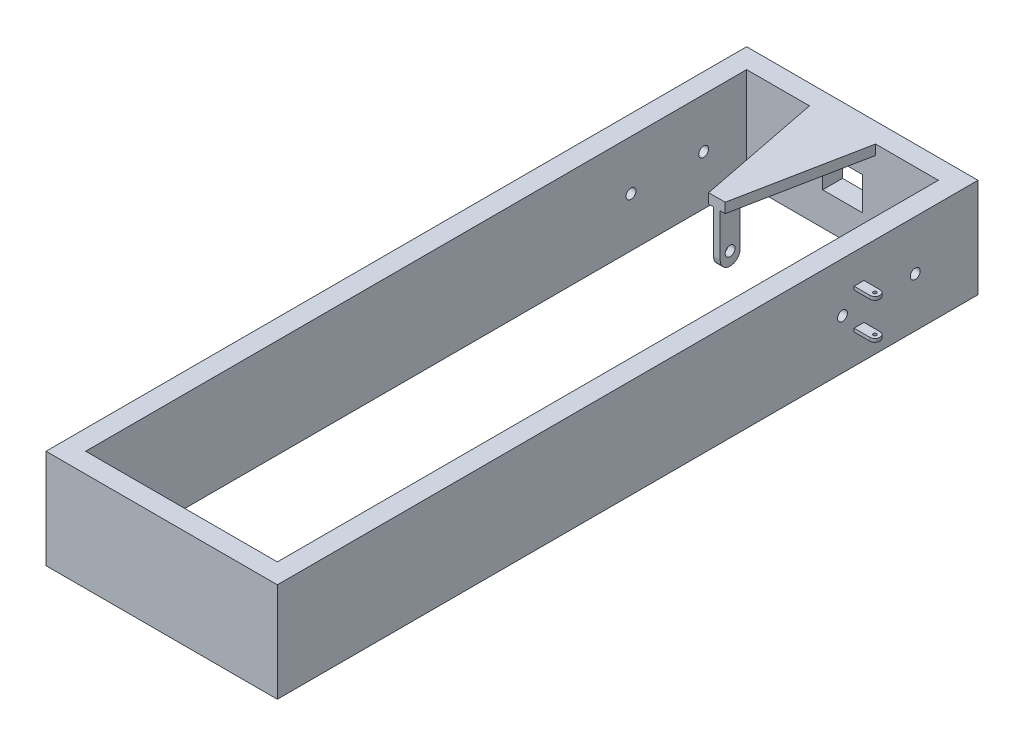
SolidWorks part; units mm, degrees
ref_plane "Front Plane" through (0, 0, 0) normal (0, 0, 1) x (1, 0, 0)
ref_plane "Top Plane" through (0, 0, 0) normal (0, 1, 0) x (1, 0, 0)
ref_plane "Right Plane" through (0, 0, 0) normal (1, 0, 0) x (0, 0, -1)
sketch "Sketch1" plane through (0, 0, 0) normal (0, 1, 0) x (1, 0, 0)
  line L1 (-29, 100) -> (29, 100)
  line L2 (-29, 100) -> (-29, -100)
  line L3 (-29, -100) -> (29, -100)
  line L4 (29, 100) -> (29, -100)
  line L5 (-29, 100) -> (29, -100) construction
  line L6 (-29, -100) -> (29, 100) construction
  line L7 (-35, 106) -> (35, 106)
  line L8 (-35, 106) -> (-35, -106)
  line L9 (-35, -106) -> (35, -106)
  line L10 (35, 106) -> (35, -106)
  line L11 (-35, 106) -> (35, -106) construction
  line L12 (-35, -106) -> (35, 106) construction
  point P0 (0, 0)
  point P6 (0, 0)
  dimension "D1" = 58
  dimension "D2" = 6
  dimension "D3" = 6
  dimension "D4" = 200
extrude "Boss-Extrude1" add sketch "Sketch1" along normal blind 30
ref_plane "Plane1" through (0, 0, -62) normal (0, 0, 1) x (1, 0, 0)
sketch "Sketch7" plane through (0, 0, -100) normal (0, 0, 1) x (1, 0, 0)
  line L0 (-35, 30) -> (35, 30) construction
  line L1 (-10, 30) -> (10, 30)
  line L2 (-10, 30) -> (-10, 27)
  line L3 (-10, 27) -> (10, 27)
  line L4 (10, 30) -> (10, 27)
  line L5 (-35, 30) -> (-35, 0) construction
  dimension "D1" = 3
  dimension "D2" = 20
  dimension "D3" = 25
sketch "Sketch8" plane through (0, 0, -62) normal (0, 0, 1) x (1, 0, 0)
  line L0 (-10, 30) -> (10, 30) construction
  line L1 (-2.5, 30) -> (2.5, 30)
  line L2 (-2.5, 30) -> (-2.5, 27)
  line L3 (-2.5, 27) -> (2.5, 27)
  line L4 (2.5, 30) -> (2.5, 27)
  line L5 (-10, 27) -> (10, 27) construction
  line L6 (10, 30) -> (10, 27) construction
  dimension "D1" = 5
  dimension "D2" = 7.5
sketch "Sketch9" plane through (0, 30, 0) normal (0, 1, 0) x (1, 0, 0)
  line L0 (10, 100) -> (2.5, 62)
  line L1 (-10, 100) -> (10, 100) construction
  line L2 (-2.5, 62) -> (2.5, 62) construction
  line L3 (-16.5058, 62) -> (16.5058, 62) construction
  line L4 (-10, 100) -> (-2.5, 62)
loft "Loft3" add profiles "Sketch7", "Sketch8"
sketch "Sketch10" plane through (0, 27, 0) normal (0, -1, 0) x (1, 0, 0)
  line L0 (-10, -100) -> (10, -100) construction
  line L1 (-1, -62) -> (1, -62)
  line L2 (-1, -62) -> (-1, -68)
  line L3 (-1, -68) -> (1, -68)
  line L4 (1, -62) -> (1, -68)
  line L6 (-2.5, -62) -> (2.5, -62) construction
  point P5 (1, -65)
  point P10 (0, -62)
  point P11 (0, -62)
  dimension "D1" = 2
  dimension "D2" = 35
  dimension "D3" = 0
  dimension "D4" = 0
extrude "Boss-Extrude3" add sketch "Sketch10" along normal blind 16
fillet "Fillet2" radius 3 2 edges at (0, 11, -68) (0, 11, -62)
sketch "Sketch2" plane through (35, 0, 0) normal (1, 0, 0) x (0, 0, -1)
  line L0 (106, 30) -> (106, 0) construction
  line L1 (-106, 30) -> (106, 30) construction
  circle A0 centre (65, 15) radius 1.5
  circle A1 centre (87, 15) radius 1.5
  dimension "D2" = 15
  dimension "D3" = 3
  dimension "D5" = 3
  dimension "D1" = 19
  dimension "D4" = 22
extrude "Cut-Extrude1" cut sketch "Sketch2" against normal through all
sketch "Sketch3" plane through (0, 0, -106) normal (0, 0, -1) x (-1, 0, 0)
  line L0 (35, 30) -> (35, 0) construction
  line L1 (-6, 20) -> (6, 20)
  line L2 (-6, 20) -> (-6, 10)
  line L3 (-6, 10) -> (6, 10)
  line L4 (6, 20) -> (6, 10)
  line L5 (-6, 20) -> (6, 10) construction
  line L6 (-6, 10) -> (6, 20) construction
  line L8 (-35, 0) -> (35, 0) construction
  point P0 (0, 15)
  dimension "D1" = 10
  dimension "D2" = 12
  dimension "D3" = 29
  dimension "D4" = 10
extrude "Cut-Extrude2" cut sketch "Sketch3" against normal up to next
sketch "Sketch11" plane through (35, 0, 0) normal (1, 0, 0) x (0, 0, -1)
  line L0 (65, 15) -> (72.7738, 15) construction
  line L1 (68.5, 20) -> (71.5, 20)
  line L2 (68.5, 20) -> (68.5, 21)
  line L3 (68.5, 21) -> (71.5, 21)
  line L4 (71.5, 20) -> (71.5, 21)
  line L5 (71.5, 10) -> (71.5, 9)
  line L6 (68.5, 9) -> (71.5, 9)
  line L7 (68.5, 10) -> (68.5, 9)
  line L8 (68.5, 10) -> (71.5, 10)
  point P7 (70, 20)
  dimension "D1" = 3
  dimension "D2" = 1
  dimension "D3" = 6
  dimension "D4" = 5
extrude "Boss-Extrude4" add sketch "Sketch11" along normal blind 6.3
fillet "Fillet3" radius 1.5 4 edges at (41.3, 9.5, -68.5) (41.3, 9.5, -71.5) (41.3, 20.5, -68.5) (41.3, 20.5, -71.5)
sketch "Sketch12" plane through (0, 21, 0) normal (0, 1, 0) x (1, 0, 0)
  circle A0 centre (39.8, 70) radius 0.5
extrude "Cut-Extrude3" cut sketch "Sketch12" against normal through all
mirror "Mirror1" about plane through (0, 0, 0) normal (1, 0, 0) of "Cut-Extrude3", "Fillet3", "Boss-Extrude4"
